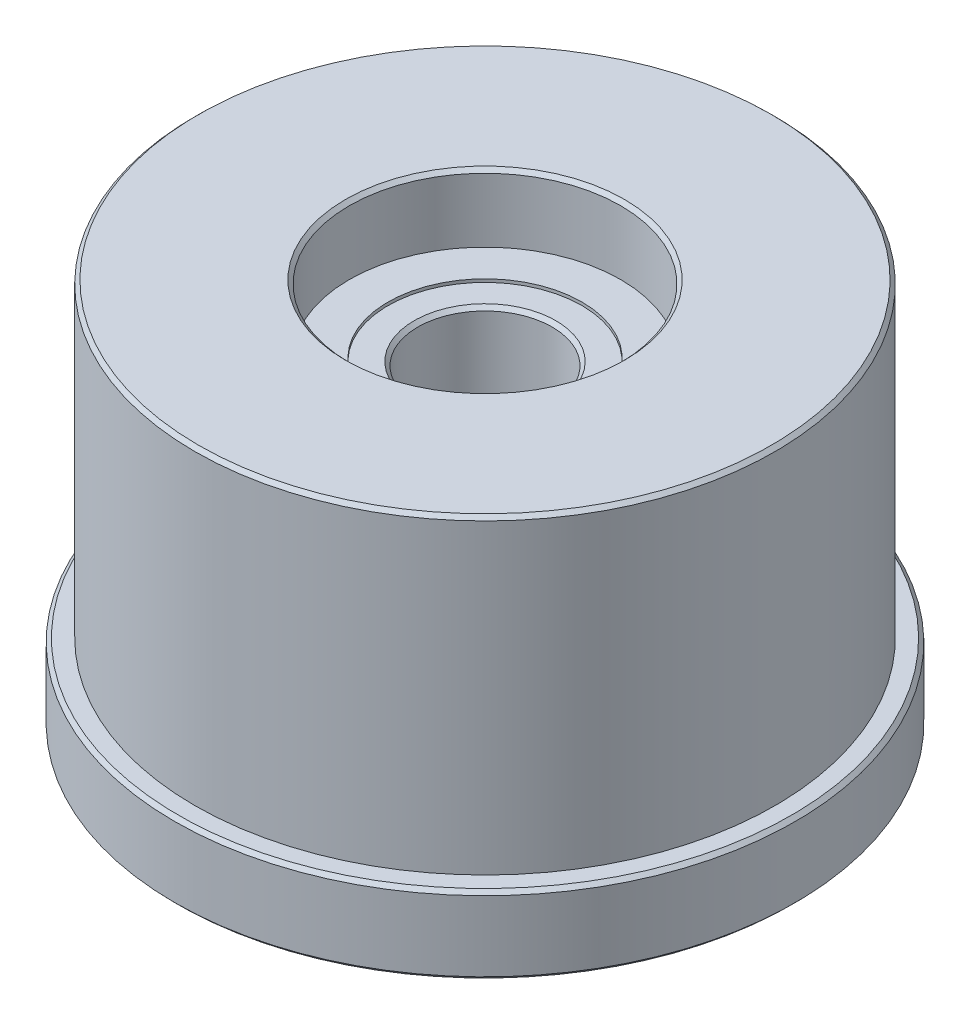
SolidWorks part; units mm, degrees
material "Nylon 101"
ref_plane "Front Plane" through (0, 0, 0) normal (0, 0, 1) x (1, 0, 0)
ref_plane "Top Plane" through (0, 0, 0) normal (0, 1, 0) x (1, 0, 0)
ref_plane "Right Plane" through (0, 0, 0) normal (1, 0, 0) x (0, 0, -1)
sketch "Sketch1" plane through (0, 0, 0) normal (0, 1, 0) x (1, 0, 0)
  circle A0 centre (0, 0) radius 23.749
  dimension "D1" = 47.498
extrude "Boss-Extrude1" add sketch "Sketch1" along normal blind 25.4
sketch "Sketch2" plane through (0, 0, 0) normal (0, -1, 0) x (1, 0, 0)
  circle A0 centre (0, 0) radius 25.4
  dimension "D1" = 50.8
extrude "Boss-Extrude2" add sketch "Sketch2" along normal blind 6.35
sketch "Sketch3" plane through (0, -6.35, 0) normal (0, -1, 0) x (1, 0, 0)
  circle A0 centre (0, 0) radius 5.5
  dimension "D1" = 11
extrude "Cut-Extrude1" cut sketch "Sketch3" against normal through all
sketch "Sketch4" plane through (0, -6.35, 0) normal (0, -1, 0) x (1, 0, 0)
  circle A0 centre (0, 0) radius 11.1125
  dimension "D1" = 22.225
extrude "Cut-Extrude2" cut sketch "Sketch4" against normal blind 5.5372
sketch "Sketch5" plane through (0, -0.8128, 0) normal (0, -1, 0) x (1, 0, 0)
  circle A0 centre (0, 0) radius 7.9375
  dimension "D1" = 15.875
extrude "Cut-Extrude3" cut sketch "Sketch5" against normal blind 0.254
ref_plane "Plane1" through (0, 9.525, 0) normal (0, 1, 0) x (1, 0, 0)
mirror "Mirror1" about plane through (0, 9.525, 0) normal (0, 1, 0) of "Cut-Extrude2", "Cut-Extrude3"
chamfer "Chamfer1" distance 0.3 angle 45 7 edges at (0, 0, -25.4) (0, -6.35, -25.4) (0, -6.35, -11.1125) (0, 25.4, 23.749) (0, 19.6088, 5.5) (0, -0.5588, -5.5) (0, 25.4, -11.1125)
equation "\"D1@Chamfer1\"=.3mm"
